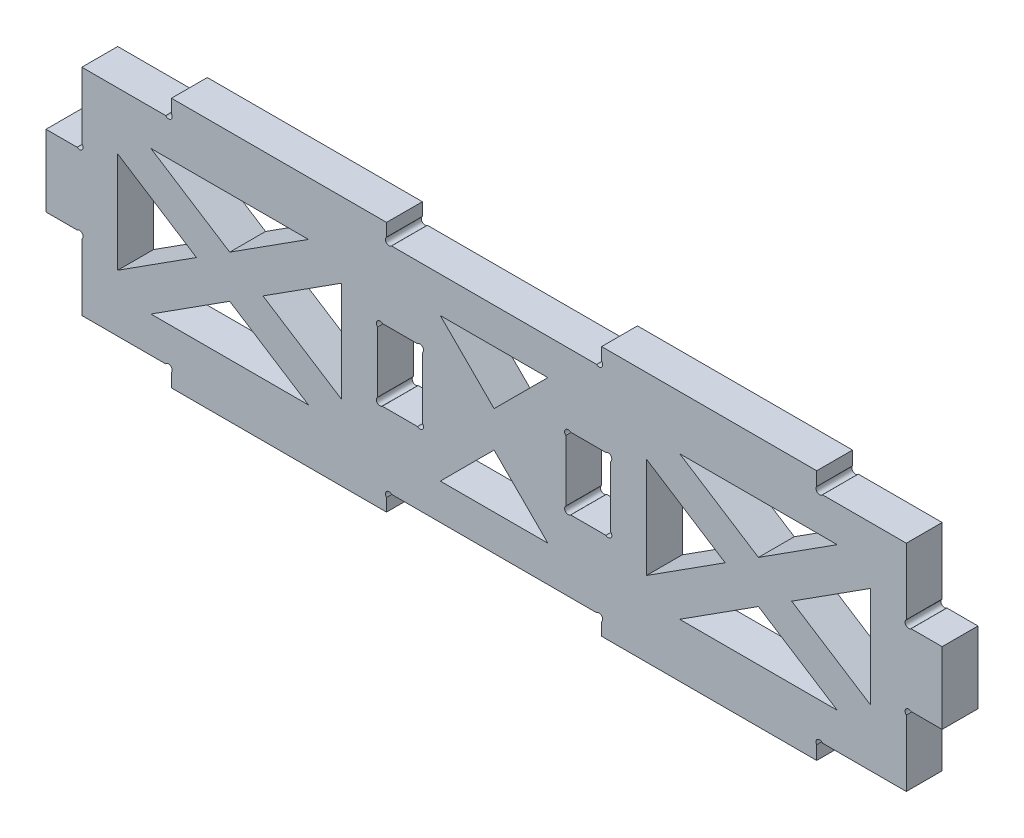
SolidWorks part; units mm, degrees
material "7050-T73510"
ref_plane "Front Plane" through (0, 0, 0) normal (0, 0, 1) x (1, 0, 0)
ref_plane "Top Plane" through (0, 0, 0) normal (0, 1, 0) x (1, 0, 0)
ref_plane "Right Plane" through (0, 0, 0) normal (1, 0, 0) x (0, 0, -1)
sketch "Sketch1" plane through (0, 0, 0) normal (0, 0, 1) x (1, 0, 0)
  line L1 (-158.75, -38.1) -> (158.75, -38.1)
  line L2 (-158.75, -38.1) -> (-158.75, 38.1)
  line L3 (-158.75, 38.1) -> (158.75, 38.1)
  line L4 (158.75, -38.1) -> (158.75, 38.1)
  line L5 (-158.75, -38.1) -> (158.75, 38.1) construction
  line L6 (-158.75, 38.1) -> (158.75, -38.1) construction
  point P0 (0, 0)
  dimension "D1" = 317.5
  dimension "D2" = 76.2
extrude "Boss-Extrude1" add sketch "Sketch1" along normal blind 12.7 contours L1 L3 region at (0, 0, 0)
sketch "Sketch2" plane through (0, 0, 12.7) normal (0, 0, 1) x (1, 0, 0)
  line L0 (-158.75, -38.1) -> (158.75, -38.1) construction
  line L1 (-38.1, -38.1) -> (-114.3, -38.1)
  line L2 (-38.1, -38.1) -> (-38.1, -44.45)
  line L3 (-38.1, -44.45) -> (-114.3, -44.45)
  line L4 (-114.3, -38.1) -> (-114.3, -44.45)
  line L5 (0, -55) -> (0, 55) construction
  line L6 (38.1, -44.45) -> (114.3, -44.45)
  line L7 (114.3, -38.1) -> (114.3, -44.45)
  line L8 (38.1, -38.1) -> (114.3, -38.1)
  line L9 (38.1, -38.1) -> (38.1, -44.45)
  line L10 (55, 0) -> (-55, 0) construction
  line L11 (38.1, 38.1) -> (38.1, 44.45)
  line L12 (38.1, 38.1) -> (114.3, 38.1)
  line L13 (114.3, 38.1) -> (114.3, 44.45)
  line L14 (38.1, 44.45) -> (114.3, 44.45)
  line L15 (-38.1, 44.45) -> (-114.3, 44.45)
  line L16 (-114.3, 38.1) -> (-114.3, 44.45)
  line L17 (-38.1, 38.1) -> (-114.3, 38.1)
  line L18 (-38.1, 38.1) -> (-38.1, 44.45)
  point P12 (-38.1, -41.275)
  dimension "D1" = 76.2
  dimension "D2" = 6.35
  dimension "D3" = 76.2
extrude "Boss-Extrude2" add sketch "Sketch2" against normal blind 12.7
sketch "Sketch3" plane through (0, 0, 12.7) normal (0, 0, 1) x (1, 0, 0)
  line L0 (55, 0) -> (-55, 0) construction
  line L1 (-158.75, -38.1) -> (-146.05, -38.1)
  line L2 (-158.75, -38.1) -> (-158.75, -12.7)
  line L3 (-158.75, -12.7) -> (-146.05, -12.7)
  line L4 (-146.05, -38.1) -> (-146.05, -12.7)
  line L6 (-158.75, 12.7) -> (-146.05, 12.7)
  line L7 (-146.05, 38.1) -> (-146.05, 12.7)
  line L8 (-158.75, 38.1) -> (-146.05, 38.1)
  line L9 (-158.75, 38.1) -> (-158.75, 12.7)
  line L10 (0, -55) -> (0, 55) construction
  line L11 (158.75, 38.1) -> (158.75, 12.7)
  line L12 (158.75, 38.1) -> (146.05, 38.1)
  line L13 (146.05, 38.1) -> (146.05, 12.7)
  line L14 (158.75, 12.7) -> (146.05, 12.7)
  line L15 (158.75, -12.7) -> (146.05, -12.7)
  line L16 (146.05, -38.1) -> (146.05, -12.7)
  line L17 (158.75, -38.1) -> (146.05, -38.1)
  line L18 (158.75, -38.1) -> (158.75, -12.7)
  line L19 (25.4, 12.7) -> (41.275, 12.7)
  line L20 (25.4, 12.7) -> (25.4, -12.7)
  line L21 (25.4, -12.7) -> (41.275, -12.7)
  line L22 (41.275, 12.7) -> (41.275, -12.7)
  line L23 (-38.1, -38.1) -> (38.1, -38.1) construction
  line L24 (-25.4, -12.7) -> (-41.275, -12.7)
  line L25 (-41.275, 12.7) -> (-41.275, -12.7)
  line L26 (-25.4, 12.7) -> (-41.275, 12.7)
  line L27 (-25.4, 12.7) -> (-25.4, -12.7)
  line L28 (-38.1, 38.1) -> (38.1, 38.1) construction
  dimension "D1" = 25.4
  dimension "D2" = 12.7
  dimension "D3" = 50.8
  dimension "D4" = 15.875
  dimension "D5" = 25.4
  dimension "D6" = 25.4
extrude "Cut-Extrude1" cut sketch "Sketch3" against normal through all
sketch "Sketch4" plane through (0, 0, 12.7) normal (0, 0, 1) x (1, 0, 0)
  line L0 (6.985, 0) -> (-6.985, 0) construction
  line L1 (-133.35, -25.4) -> (-53.975, -25.4)
  line L2 (-133.35, -25.4) -> (-133.35, 25.4)
  line L3 (-133.35, 25.4) -> (-53.975, 25.4)
  line L4 (-53.975, -25.4) -> (-53.975, 25.4)
  line L5 (-133.35, 25.4) -> (-133.4571, 24.9525)
  line L6 (-19.05, 25.4) -> (0, 6.35)
  line L7 (-146.05, 12.7) -> (-146.05, 38.1) construction
  line L8 (-41.275, 12.7) -> (-41.275, -12.7) construction
  line L9 (-146.05, 38.1) -> (-114.3, 38.1) construction
  line L10 (-133.35, 25.4) -> (-53.975, -25.4) construction
  line L11 (-133.35, -25.4) -> (-53.975, 25.4) construction
  line L12 (-133.35, 17.8609) -> (-105.4424, 0)
  line L13 (-121.5701, -25.4) -> (-93.6625, -7.5391)
  line L14 (-121.5701, 25.4) -> (-93.6625, 7.5391)
  line L15 (-133.35, -17.8609) -> (-105.4424, 0)
  line L16 (0, -6.985) -> (0, 6.985) construction
  line L17 (0, 6.35) -> (19.05, 25.4)
  line L18 (-129.927, -30.7484) -> (-50.552, 20.0516) construction
  line L19 (0, -6.35) -> (19.05, -25.4)
  line L20 (-136.773, -20.0516) -> (-57.398, 30.7484) construction
  line L21 (-136.773, 20.0516) -> (-57.398, -30.7484) construction
  line L22 (-129.927, 30.7484) -> (-50.552, -20.0516) construction
  line L23 (-81.8826, 0) -> (-53.975, 17.8609)
  line L24 (-93.6625, -7.5391) -> (-65.7549, -25.4)
  line L25 (-19.05, -25.4) -> (0, -6.35)
  line L26 (-38.1, -38.1) -> (38.1, -38.1) construction
  line L42 (-19.05, -25.4) -> (19.05, -25.4)
  line L43 (-146.05, -38.1) -> (-114.3, -38.1) construction
  line L44 (-19.05, -25.4) -> (-19.05, 25.4)
  line L45 (-19.05, 25.4) -> (19.05, 25.4)
  line L46 (19.05, -25.4) -> (19.05, 25.4)
  line L56 (-93.6625, 7.5391) -> (-65.7549, 25.4)
  line L57 (-81.8826, 0) -> (-53.975, -17.8609)
  point P0 (-93.6625, 0)
  point P54 (0, 0)
  dimension "D1" = 12.7
  dimension "D2" = 12.7
  dimension "D3" = 12.7
  dimension "D7" = 12.7
  dimension "D10" = 12.7
  dimension "D9" = 12.7
  dimension "D8" = 38.1
  dimension "D4" = 6.35
  dimension "D5" = 6.35
sketch "Sketch7" plane through (0, 0, 12.7) normal (0, 0, 1) x (1, 0, 0)
  line L0 (0, -6.985) -> (0, 6.985) construction
  line L1 (6.985, 0) -> (-6.985, 0) construction
  circle A1 centre (-115.3222, -38.8536) radius 1.27
  circle A2 centre (-37.2199, -39.0156) radius 1.27
  circle A3 centre (37.2199, -39.0156) radius 1.27
  circle A4 centre (115.3222, -38.8536) radius 1.27
  circle A7 centre (115.3222, 38.8536) radius 1.27
  circle A8 centre (37.2199, 39.0156) radius 1.27
  circle A9 centre (-37.2199, 39.0156) radius 1.27
  circle A10 centre (-115.3222, 38.8536) radius 1.27
  circle A12 centre (-146.8896, -13.6529) radius 1.27
  circle A15 centre (-146.8896, 13.6529) radius 1.27
  circle A16 centre (146.8896, -13.6529) radius 1.27
  circle A17 centre (146.8896, 13.6529) radius 1.27
  point P29 (146.8896, 13.6529)
  dimension "D1" = 2.54
  dimension "D2" = 2.54
extrude "Cut-Extrude4" cut sketch "Sketch7" against normal through all
sketch "Sketch8" plane through (0, 0, 12.7) normal (0, 0, 1) x (1, 0, 0)
  line L0 (6.985, 0) -> (-6.985, 0) construction
  line L1 (0, -6.985) -> (0, 6.985) construction
  circle A0 centre (-40.4413, 11.7419) radius 1.27
  circle A1 centre (-26.2661, 11.7711) radius 1.27
  circle A2 centre (-26.2661, -11.7711) radius 1.27
  circle A3 centre (-40.4413, -11.7419) radius 1.27
  circle A4 centre (40.4413, -11.7419) radius 1.27
  circle A5 centre (26.2661, -11.7711) radius 1.27
  circle A6 centre (26.2661, 11.7711) radius 1.27
  circle A7 centre (40.4413, 11.7419) radius 1.27
extrude "Cut-Extrude5" cut sketch "Sketch8" against normal through all
extrude "Cut-Extrude6" cut sketch "Sketch4" against normal through all contours L24 L13 L1 | L2 L15 L12 | L14 L56 L3 | L23 L57 L4 | L25 L42 L19 | L45 L6 L17 region at (-93.6625, -19.4464, 12.7) region at (-124.0475, 0, 12.7) region at (-63.2775, 0, 12.7) region at (-93.6625, 19.4464, 12.7) region at (0, 19.05, 12.7) region at (0, -19.05, 12.7)
mirror "Mirror1" about plane through (0, 0, 0) normal (1, 0, 0) of "Cut-Extrude6"
